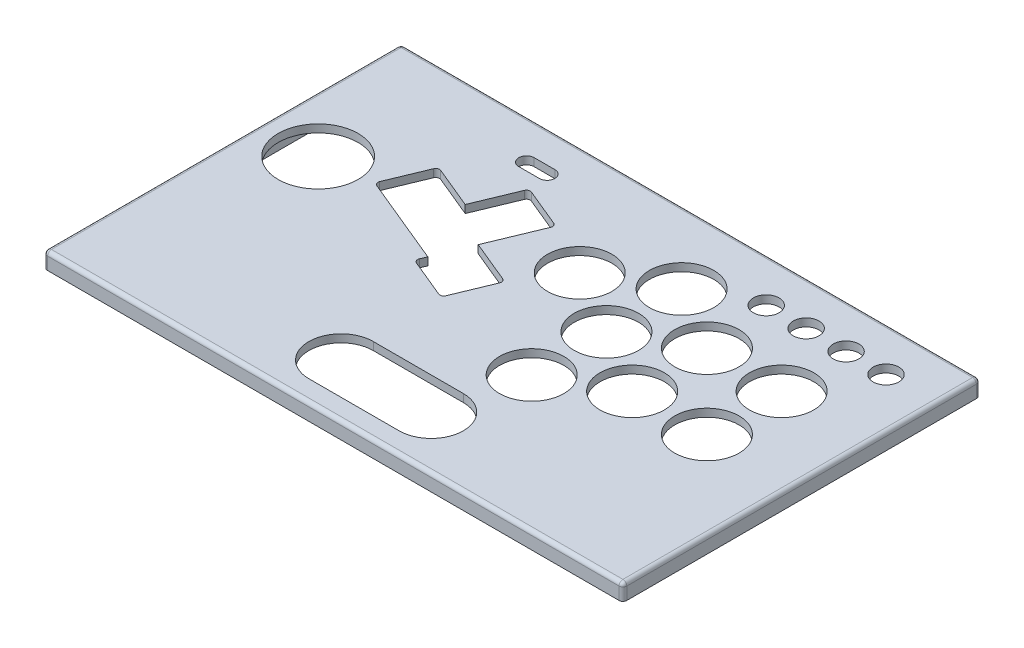
SolidWorks part; units mm, degrees
ref_plane "Front Plane" through (0, 0, 0) normal (0, 0, 1) x (1, 0, 0)
ref_plane "Top Plane" through (0, 0, 0) normal (0, 1, 0) x (1, 0, 0)
ref_plane "Right Plane" through (0, 0, 0) normal (1, 0, 0) x (0, 0, -1)
sketch "Button Cutouts" plane through (0, 0, 0) normal (0, 1, 0) x (1, 0, 0)
  line L0 (24.5, 61) -> (24.5, 32) construction
  line L1 (298.8548, 529.5585) -> (1494.2739, 529.5585) construction
  line L12 (-36.2591, 48.1292) -> (-29.3708, 64.7591) construction
  line L20 (49.5, 75) -> (49.5, 46) construction
  line L21 (78.5, 75) -> (78.5, 46) construction
  line L22 (17.5, 0) -> (-17.5, 0) construction
  line L28 (-36.2591, 48.1292) -> (-19.6292, 41.2409) construction
  line L29 (17.5, -12.5) -> (-17.5, -12.5)
  line L30 (17.5, 12.5) -> (-17.5, 12.5)
  line L31 (24.6803, 89.9994) -> (49.5, 75) construction
  line L32 (24.6803, 89.9994) -> (24.5, 61) construction
  line L33 (-0.5241, 75.6559) -> (24.6803, 89.9994) construction
  line L34 (-0.5241, 75.6559) -> (24.5, 61) construction
  line L48 (-29.3708, 64.7591) -> (-12.7409, 57.8708) construction
  line L49 (-19.6292, 41.2409) -> (-12.7409, 57.8708) construction
  line L50 (-36.2591, 48.1292) -> (-12.7409, 57.8708) construction
  line L51 (-29.3708, 64.7591) -> (-19.6292, 41.2409) construction
  line L52 (-35.6984, 52.2266) -> (-28.8101, 68.8564) construction
  line L53 (-35.6984, 52.2266) -> (-52.3282, 59.1149) construction
  line L54 (-28.8101, 68.8564) -> (-45.4399, 75.7447) construction
  line L55 (-52.3282, 59.1149) -> (-45.4399, 75.7447) construction
  line L56 (-35.6984, 52.2266) -> (-45.4399, 75.7447) construction
  line L57 (-28.8101, 68.8564) -> (-52.3282, 59.1149) construction
  line L58 (-69.9281, 66.405) -> (-63.0398, 83.0348) construction
  line L59 (-69.9281, 66.405) -> (-53.2983, 59.5167) construction
  line L60 (-63.0398, 83.0348) -> (-46.41, 76.1465) construction
  line L61 (-53.2983, 59.5167) -> (-46.41, 76.1465) construction
  line L62 (-69.9281, 66.405) -> (-46.41, 76.1465) construction
  line L63 (-63.0398, 83.0348) -> (-53.2983, 59.5167) construction
  line L64 (-40.5692, 63.9856) -> (-22.9693, 56.6955) construction
  line L65 (-40.5692, 63.9856) -> (-58.1691, 71.2758) construction
  line L66 (-45.0381, 76.7148) -> (-38.1498, 93.3446) construction
  line L67 (-45.0381, 76.7148) -> (-28.4083, 69.8265) construction
  line L68 (-38.1498, 93.3446) -> (-21.52, 86.4563) construction
  line L69 (-28.4083, 69.8265) -> (-21.52, 86.4563) construction
  line L70 (-45.0381, 76.7148) -> (-21.52, 86.4563) construction
  line L71 (-38.1498, 93.3446) -> (-28.4083, 69.8265) construction
  line L72 (-40.5692, 63.9856) -> (-33.2791, 81.5855) construction
  line L73 (-24.5, 53) -> (-22.9693, 56.6955) construction
  line L74 (-58.1691, 71.2758) -> (-65.4592, 53.6759) construction
  line L75 (-65.4592, 53.6759) -> (-90.4039, 64.0083) construction
  line L76 (-70.5814, 66.1344) -> (-63.3104, 83.6881)
  line L77 (-63.3104, 83.6881) -> (-45.7105, 76.398)
  line L78 (-45.7105, 76.398) -> (-38.4204, 93.9979)
  line L79 (-38.4204, 93.9979) -> (-20.8667, 86.7269)
  line L80 (-20.8667, 86.7269) -> (-29.6876, 65.4315)
  line L81 (-29.6876, 65.4315) -> (-12.0877, 58.1414)
  line L82 (-12.0877, 58.1414) -> (-19.3586, 40.5877)
  line L83 (-19.3586, 40.5877) -> (-36.9123, 47.8586)
  line L84 (-36.9123, 47.8586) -> (-35.3816, 51.5542)
  line L85 (-35.3816, 51.5542) -> (-70.5814, 66.1344)
  line L86 (-66.484, 74.7199) -> (-66.9459, 74.9112) construction
  line L87 (-29.6436, 90.3624) -> (-29.8349, 89.9005) construction
  line L88 (-16.1851, 49.5558) -> (-15.7231, 49.3645) construction
  line L89 (-33.2791, 140.3317) -> (-33.2791, 81.5855) construction
  circle A0 centre (24.5, 32) radius 12.5
  circle A1 centre (24.5, 61) radius 12.5
  circle A2 centre (49.5, 46) radius 12.5
  circle A3 centre (49.5, 75) radius 12.5
  circle A4 centre (78.5, 75) radius 12.5
  circle A5 centre (78.5, 46) radius 12.5
  arc A8 (17.5, -12.5) -> (17.5, 12.5) centre (17.5, 0) ccw
  arc A9 (-17.5, 12.5) -> (-17.5, -12.5) centre (-17.5, 0) ccw
  circle A10 centre (-90.4039, 64.0083) radius 15.5
  circle A11 centre (24.6803, 89.9994) radius 12.5
  circle A12 centre (-0.5241, 75.6559) radius 12.5
  point P1 (-24.5, 53)
  point P5 (-40.5692, 63.9856)
  point P6 (-58.1691, 71.2758)
  point P37 (0, 0)
  point P45 (-33.2791, 81.5855)
  point P54 (-30, 0)
  point P55 (30, 0)
  dimension "D2" = 25
  dimension "D12" = 12.5
  dimension "D18" = 31
  dimension "D25" = 22.5
  dimension "D1" = 29
  dimension "D3" = 25
  dimension "D4" = 29
  dimension "D5" = 14
  dimension "D6" = 18
  dimension "D7" = 19.05
  dimension "D8" = 53
  dimension "D9" = 7
  dimension "D10" = 4
  dimension "D11" = 27
  dimension "D13" = 32
  dimension "D14" = 7
  dimension "D15" = 19.05
  dimension "D16" = 0.5
  dimension "D17" = 60
  dimension "D19" = 0.5
  dimension "D20" = 0.5
  dimension "D21" = 29
  dimension "D22" = 29
  dimension "D23" = 0.5
  dimension "D24" = 0.5
sketch "Sketch2" plane through (0, 0, 0) normal (0, 1, 0) x (1, 0, 0)
  line L0 (-105.9039, 64.0083) -> (-112.4039, 64.0083) construction
  line L1 (-112.4039, 118.1994) -> (112.4039, 118.1994)
  line L2 (-112.4039, 118.1994) -> (-112.4039, -20.5)
  line L3 (-112.4039, -20.5) -> (112.4039, -20.5)
  line L4 (112.4039, 118.1994) -> (112.4039, -20.5)
  line L5 (24.6803, 102.4994) -> (24.6803, 118.1994) construction
  line L6 (0, -12.5) -> (0, -20.5) construction
  line L7 (17.5, -12.5) -> (-17.5, -12.5) construction
  circle A0 centre (-90.4039, 64.0083) radius 15.5 construction
  circle A2 centre (24.6803, 89.9994) radius 12.5 construction
  point P4 (0, -20.5)
  dimension "D2" = 6.5
  dimension "D1" = 8
  dimension "D3" = 15.7
extrude "top plate" add sketch "Sketch2" along normal blind 6.35
extrude "primary button cutouts" cut sketch "Button Cutouts" along normal up to next
fillet "Fillet1" radius 1.5 7 edges at (-20.8667, 3.175, -86.7269) (-12.0877, 3.175, -58.1414) (-19.3586, 3.175, -40.5877) (-36.9123, 3.175, -47.8586) (-70.5814, 3.175, -66.1344) (-63.3104, 3.175, -83.6881) (-38.4204, 3.175, -93.9979)
sketch "Sketch4" plane through (0, 0, 0) normal (0, -1, 0) x (1, 0, 0)
  line L0 (112.4039, 20.5) -> (112.4039, -118.1994) construction
  line L1 (-106.4039, 14.5) -> (106.4039, 14.5)
  line L2 (-106.4039, 14.5) -> (-106.4039, -112.1994)
  line L3 (-106.4039, -112.1994) -> (106.4039, -112.1994)
  line L4 (106.4039, 14.5) -> (106.4039, -112.1994)
  line L5 (-112.4039, 20.5) -> (112.4039, 20.5) construction
  line L6 (112.4039, -118.1994) -> (-112.4039, -118.1994) construction
  line L7 (-112.4039, -118.1994) -> (-112.4039, 20.5) construction
  dimension "D1" = 6
  dimension "D2" = 6
  dimension "D3" = 6
  dimension "D4" = 6
extrude "Cut-Extrude2" cut sketch "Sketch4" against normal blind 3.3
fillet "Fillet2" radius 1.5 8 edges at (112.4039, 3.175, -118.1994) (-112.4039, 3.175, -118.1994) (-112.4039, 3.175, 20.5) (112.4039, 3.175, 20.5) (112.4039, 6.35, -48.8497) (0, 6.35, -118.1994) (0, 6.35, 20.5) (-112.4039, 6.35, -48.8497)
sketch "Sketch5" plane through (0, 0, 0) normal (0, -1, 0) x (1, 0, 0)
  line L0 (110.9039, -118.1994) -> (-110.9039, -118.1994) construction
  line L1 (-91.4039, -112.1994) -> (-56.4039, -112.1994)
  line L2 (-91.4039, -112.1994) -> (-91.4039, -118.1994)
  line L3 (-91.4039, -118.1994) -> (-56.4039, -118.1994)
  line L4 (-56.4039, -112.1994) -> (-56.4039, -118.1994)
  line L5 (-56.4039, -112.1994) -> (-56.4039, -118.1994) construction
extrude "Cut-Extrude3" cut sketch "Sketch5" against normal blind 3
hole_wizard "Tap Drill for M3x0.5 Tap1" positions "3DSketch1" profile "Sketch6" hole size "M3x0.5" standard "ANSI Metric"
sketch3d "3DSketch1"
  line L0 (-108.4039, 0, 16.5) -> (-108.4039, 0, 20.5) construction
  line L1 (-110.9039, 0, 20.5) -> (110.9039, 0, 20.5) construction
  line L3 (-108.4039, 0, 16.5) -> (-112.4039, 0, 16.5)
  line L4 (-112.4039, 0, -116.6994) -> (-112.4039, 0, 19) construction
  line L6 (108.4039, 0, -114.1994) -> (112.4039, 0, -114.1994)
  line L7 (112.4039, 0, 19) -> (112.4039, 0, -116.6994) construction
  line L9 (108.4039, 0, -114.1994) -> (108.4039, 0, -118.1994)
  line L10 (110.9039, 0, -118.1994) -> (-56.4039, 0, -118.1994) construction
  point P0 (-108.4039, 0, 16.5)
  point P2 (-108.4039, 0, -114.1994)
  point P4 (108.4039, 0, -114.1994)
  point P6 (108.4039, 0, 16.5)
  dimension "D1" = 4
sketch "Sketch6" plane through (-108.4039, 0, 16.5) normal (1, 0, 0) x (0, 0, -1)
  line L0 (0, 0) -> (0, 4.7511)
  line L1 (0, 4.7511) -> (1.25, 4)
  line L2 (1.25, 4) -> (1.25, 0)
  line L5 (1.25, 0) -> (0, 0)
  line L10 (0, 4.7511) -> (-1.25, 4) construction
  line L11 (0, -6.35) -> (0, 107.95) construction
  dimension "Hole Dia." = 2.5
  dimension "Hole Depth" = 4
  dimension "Drill Angle" = 118
sketch "Sketch7" plane through (0, 6.35, 0) normal (0, 1, 0) x (1, 0, 0)
  circle A0 centre (46.5961, 100.92) radius 5
  circle A1 centre (62.0961, 100.92) radius 5
  circle A2 centre (77.5961, 100.92) radius 5
  circle A3 centre (93.0961, 100.92) radius 5
  point P0 (93.0961, 100.92)
  dimension "D1" = 10
extrude "extra_buttons" cut sketch "Sketch7" against normal up to next
sketch "Sketch8" plane through (0, 6.35, 0) normal (0, 1, 0) x (1, 0, 0)
  line L0 (-48.0625, 102.5336) -> (-40.0625, 102.5336) construction
  line L1 (-48.0625, 105.5336) -> (-40.0625, 105.5336)
  line L2 (-48.0625, 99.5336) -> (-40.0625, 99.5336)
  arc A0 (-48.0625, 105.5336) -> (-48.0625, 99.5336) centre (-48.0625, 102.5336) ccw
  arc A1 (-40.0625, 99.5336) -> (-40.0625, 105.5336) centre (-40.0625, 102.5336) ccw
  point P2 (-44.0625, 102.5336)
  dimension "D1" = 8
  dimension "D2" = 6
extrude "led_cutout" cut sketch "Sketch8" against normal up to next
